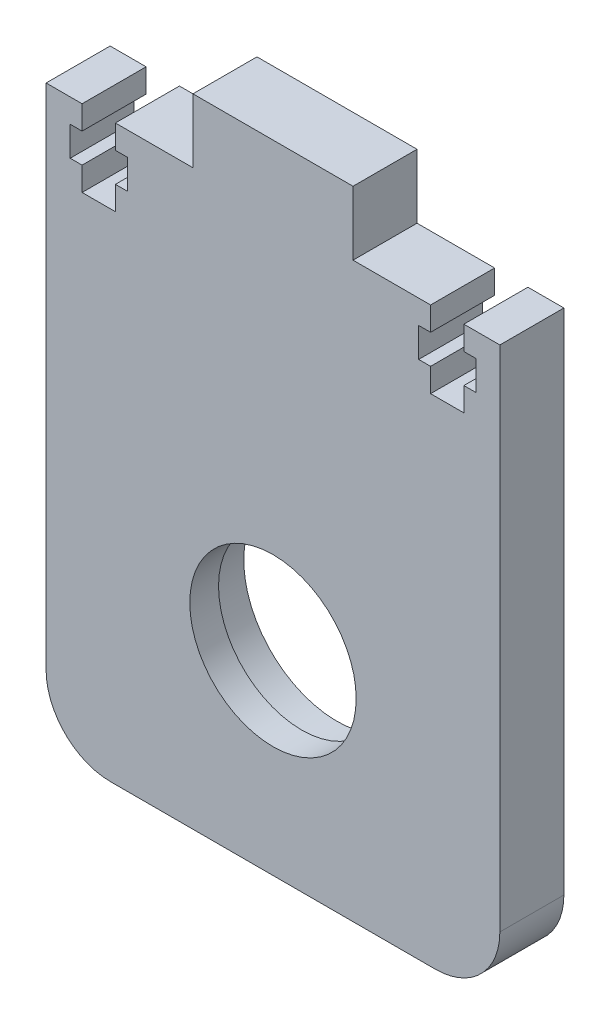
SolidWorks part; units mm, degrees
ref_plane "Front Plane" through (0, 0, 0) normal (0, 0, 1) x (1, 0, 0)
ref_plane "Top Plane" through (0, 0, 0) normal (0, 1, 0) x (1, 0, 0)
ref_plane "Right Plane" through (0, 0, 0) normal (1, 0, 0) x (0, 0, -1)
sketch "Sketch12" plane through (0, 0, 0) normal (0, 0, 1) x (1, 0, 0)
  line L0 (62.1258, 0) -> (62.1258, 113.63)
  line L1 (62.1258, 113.63) -> (152.1258, 113.63)
  line L2 (62.1258, 0) -> (152.1258, 0)
  line L3 (152.1258, 113.63) -> (152.1258, 0)
  circle A0 centre (99.6258, 37.5) radius 25.4
  circle A1 centre (99.6258, 37.5) radius 6.5
  dimension "D3" = 50.8
  dimension "D4" = 13
  dimension "D1" = 113.63
  dimension "D2" = 90
extrude "Boss-Extrude10" add sketch "Sketch12" along normal blind 12.7 separate body contours L1 L3 L2 L0
sketch "Sketch15" plane through (0, 0, 12.7) normal (0, 0, 1) x (1, 0, 0)
  line L0 (62.1258, 0) -> (152.1258, 0) construction
  circle A0 centre (107.1258, 38.6276) radius 25.4
  point P7 (107.1258, 0)
  dimension "D1" = 50.8
  dimension "D2" = 38.6276
sketch "Sketch24" plane through (0, 0, 12.7) normal (0, 0, 1) x (1, 0, 0)
  line L0 (62.1258, 113.63) -> (62.1258, 109.63)
  line L1 (62.1258, 0) -> (62.1258, 113.63) construction
  line L2 (62.1258, 109.63) -> (152.1258, 109.63)
  line L3 (152.1258, 113.63) -> (152.1258, 0) construction
  line L4 (152.1258, 109.63) -> (152.1258, 113.63)
  line L5 (152.1258, 113.63) -> (62.1258, 113.63)
  dimension "D1" = 4
sketch "Sketch25" plane through (0, 0, 12.7) normal (0, 0, 1) x (1, 0, 0)
  circle A0 centre (107.1258, 38.6276) radius 18.5
  dimension "D1" = 37
extrude "Cut-Extrude1" cut sketch "Sketch25" against normal through all
sketch "Sketch26" plane through (0, 0, 12.7) normal (0, 0, 1) x (1, 0, 0)
  circle A0 centre (107.1258, 38.6276) radius 16.5
  circle A1 centre (107.1258, 38.6276) radius 18.5
  dimension "D1" = 37
  dimension "D2" = 2
extrude "Boss-Extrude15" add sketch "Sketch26" against normal blind 5.7
fillet "Fillet1" radius 12.8 2 edges at (152.1258, 0, 6.35) (62.1258, 0, 6.35)
sketch "Sketch27" plane through (0, 0, 0) normal (0, 0, -1) x (-1, 0, 0)
  line L0 (-69.2638, 113.63) -> (-69.2638, 108.931)
  line L1 (-152.1258, 113.63) -> (-62.1258, 113.63) construction
  line L2 (-69.2638, 108.931) -> (-66.9018, 108.931)
  line L3 (-66.9018, 108.931) -> (-66.9018, 103.089)
  line L4 (-66.9018, 103.089) -> (-69.2638, 103.089)
  line L5 (-69.2638, 103.089) -> (-69.2638, 98.39)
  line L6 (-69.2638, 98.39) -> (-75.8678, 98.39)
  line L7 (-75.8678, 98.39) -> (-75.8678, 103.089)
  line L8 (-75.8678, 103.089) -> (-78.2298, 103.089)
  line L9 (-78.2298, 103.089) -> (-78.2298, 108.931)
  line L10 (-78.2298, 108.931) -> (-75.8678, 108.931)
  line L11 (-75.8678, 108.931) -> (-75.8678, 113.63)
  line L12 (-75.8678, 113.63) -> (-69.2638, 113.63)
  line L13 (-138.3838, 108.931) -> (-138.3838, 113.63)
  line L15 (-107.1258, 113.63) -> (-107.1258, 67.3255)
  line L28 (-136.0218, 108.931) -> (-138.3838, 108.931)
  line L29 (-136.0218, 103.089) -> (-136.0218, 108.931)
  line L30 (-138.3838, 103.089) -> (-136.0218, 103.089)
  line L31 (-138.3838, 98.39) -> (-138.3838, 103.089)
  line L32 (-144.9878, 98.39) -> (-138.3838, 98.39)
  line L33 (-144.9878, 103.089) -> (-144.9878, 98.39)
  line L34 (-147.3498, 103.089) -> (-144.9878, 103.089)
  line L35 (-147.3498, 108.931) -> (-147.3498, 103.089)
  line L36 (-144.9878, 108.931) -> (-147.3498, 108.931)
  line L37 (-144.9878, 113.63) -> (-144.9878, 108.931)
  line L38 (-138.3838, 113.63) -> (-144.9878, 113.63)
  point P22 (-72.5658, 113.63)
  point P29 (-141.6858, 113.63)
  line M19 (-62.1258, 113.63) -> (-152.1258, 113.63)
  dimension "D1" = 6.604
  dimension "D2" = 11.328
  dimension "D3" = 5.842
  dimension "D4" = 15.24
  dimension "D5" = 69.12
ref_axis "Axis2" through (107.1258, 113.63, 0) along (0, -1, 0)
extrude "Cut-Extrude2" cut sketch "Sketch27" against normal through all contours L11 L10 L9 L8 L7 L6 L5 L4 L3 L2 L0 M19 | L37 L36 L35 L34 L33 L32 L31 L30 L29 L28 L13 M19 region at (141.6858, 106.01, 0) region at (72.5658, 106.01, 0)
sketch "Sketch28" plane through (0, 113.63, 0) normal (0, 1, 0) x (1, 0, 0)
  line L0 (107.1258, 0) -> (91.2508, 0)
  line L1 (75.8678, 0) -> (138.3838, 0) construction
  line L2 (91.2508, 0) -> (91.2508, -12.7)
  line L3 (81.7258, -12.7) -> (132.5258, -12.7) construction
  line L4 (91.2508, -12.7) -> (123.0008, -12.7)
  line L5 (123.0008, -12.7) -> (123.0008, 0)
  line L6 (123.0008, 0) -> (107.1258, 0)
  dimension "D1" = 31.75
extrude "Boss-Extrude16" add sketch "Sketch28" along normal blind 12.7
